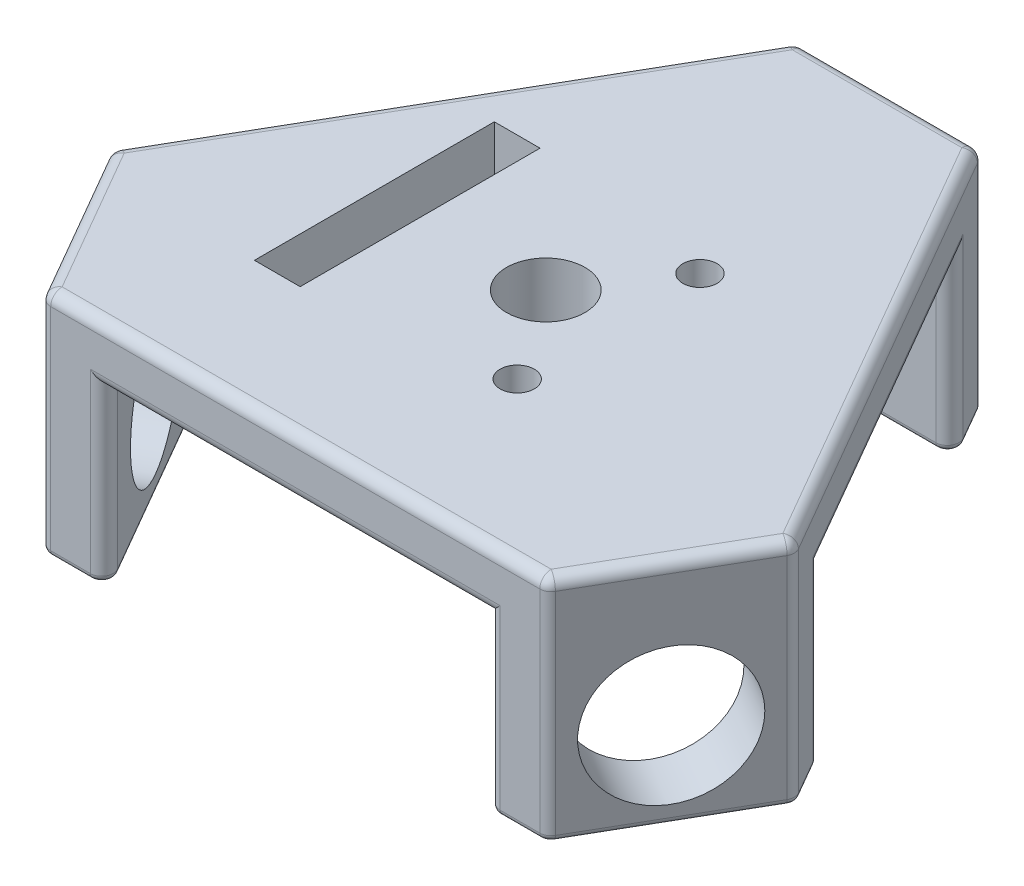
SolidWorks part; units mm, degrees
ref_plane "Front Plane" through (0, 0, 0) normal (0, 0, 1) x (1, 0, 0)
ref_plane "Top Plane" through (0, 0, 0) normal (0, 1, 0) x (1, 0, 0)
ref_plane "Right Plane" through (0, 0, 0) normal (1, 0, 0) x (0, 0, -1)
sketch "Sketch1" plane through (0, 0, 0) normal (0, 1, 0) x (1, 0, 0)
  line L0 (0, 0) -> (0, 30) construction
  line L2 (0, 0) -> (25.9808, -15) construction
  line L4 (0, 0) -> (-25.9808, -15) construction
  line L6 (0, 30) -> (8, 30)
  line L7 (25.9808, -15) -> (29.9808, -8.0718)
  line L8 (25.9808, -15) -> (21.9808, -21.9282)
  line L9 (-29.9808, -8.0718) -> (-25.9808, -15)
  line L10 (-25.9808, -15) -> (-21.9808, -21.9282)
  line L11 (0, 30) -> (-8, 30)
  line L12 (-21.9808, -21.9282) -> (21.9808, -21.9282)
  line L13 (-29.9808, -8.0718) -> (-8, 30)
  line L14 (8, 30) -> (29.9808, -8.0718)
  line L15 (0, 0) -> (-13.825, 7.9819) construction
  line L16 (0, 0) -> (13.825, 7.9819) construction
  line L17 (0, 0) -> (0, -15.9637) construction
  dimension "D2" = 8
  dimension "D3" = 8
  dimension "D4" = 90
  dimension "D5" = 30
  dimension "D6" = 30
  dimension "D7" = 30
  dimension "D1" = 6
extrude "Boss-Extrude1" add sketch "Sketch1" along normal blind 5 contours L13 | L14 L6 L11 L13 L9 L10 L12 L8 L7 | L14 | L12 region at (0, 0, 0)
sketch "Sketch2" plane through (0, 0, 0) normal (0, -1, 0) x (1, 0, 0)
  line L6 (8, -30) -> (29.9808, 8.0718)
  line L7 (29.9808, 8.0718) -> (21.9808, 21.9282)
  line L8 (21.9808, 21.9282) -> (-21.9808, 21.9282)
  line L9 (-21.9808, 21.9282) -> (-29.9808, 8.0718)
  line L10 (-29.9808, 8.0718) -> (-8, -30)
  line L11 (-8, -30) -> (8, -30)
  line L15 (-21.9808, 21.9282) -> (-29.9808, 8.0718)
  line L51 (-17.6506, 19.4282) -> (-25.6506, 5.5718)
  line L52 (-21.9808, 21.9282) -> (21.9808, 21.9282) construction
  line L53 (-29.9808, 8.0718) -> (-8, -30) construction
  line L54 (-21.9808, 21.9282) -> (-16.2073, 21.9282)
  line L55 (-29.9808, 8.0718) -> (-27.094, 3.0718)
  line L56 (-25.6506, 5.5718) -> (-16.2073, 21.9282)
  line L57 (-17.6506, 19.4282) -> (-27.094, 3.0718)
  line L58 (29.9808, 8.0718) -> (21.9808, 21.9282)
  line L59 (21.9808, 21.9282) -> (16.2073, 21.9282)
  line L60 (25.6506, 5.5718) -> (17.6506, 19.4282)
  line L61 (25.6506, 5.5718) -> (16.2073, 21.9282)
  line L62 (17.6506, 19.4282) -> (27.094, 3.0718)
  line L63 (29.9808, 8.0718) -> (27.094, 3.0718)
  line L64 (-8, -30) -> (8, -30)
  line L65 (8, -30) -> (10.8868, -25)
  line L66 (-8, -25) -> (8, -25)
  line L67 (-8, -25) -> (10.8868, -25)
  line L68 (8, -25) -> (-10.8868, -25)
  line L69 (-8, -30) -> (-10.8868, -25)
  line M7 (8, -30) -> (29.9808, 8.0718)
  line M8 (29.9808, 8.0718) -> (21.9808, 21.9282)
  line M9 (21.9808, 21.9282) -> (-21.9808, 21.9282)
  line M10 (-21.9808, 21.9282) -> (-29.9808, 8.0718)
  line M11 (-29.9808, 8.0718) -> (-8, -30)
  line M12 (-8, -30) -> (8, -30)
  dimension "D3" = 3
  dimension "D1" = 0
  dimension "D2" = 5
extrude "Boss-Extrude2" add sketch "Sketch2" along normal blind 15 contours L51 M9 M10 M11 | M7 M8 M9 | M11 M12 M7 region at (0, 0, -27.3726) region at (23.7054, 0, 13.6863) region at (-23.7054, 0, 13.6863)
sketch "Sketch4" plane through (0, 0, -30) normal (0, 0, -1) x (-1, 0, 0)
  line L0 (-10.8868, 0) -> (10.8868, 0) construction
  line L4 (10.8868, -15) -> (-10.8868, -15) construction
  line L6 (-8, 5) -> (-8, -15) construction
  line L7 (-8, -15) -> (8, -15) construction
  line L12 (8, -15) -> (8, 5) construction
  line L14 (-8, 0) -> (8, 0)
  line L21 (8, -15) -> (-8, -15)
  line L23 (-8, 0) -> (-8, -15)
  line L24 (-8, -15) -> (8, -15)
  line L25 (8, -15) -> (8, 0)
  line L31 (-8, -7.5) -> (8, -7.5) construction
  line L32 (0, 0) -> (0, -15) construction
  circle A1 centre (0, -7.5) radius 6
  dimension "D1" = 12
extrude "Cut-Extrude1" cut sketch "Sketch4" against normal up to surface (5 mm away) contours A1 region at (0, -7.5, -30) up to face at (0, -7.5, -25)
pattern_circular "CirPattern1" count 3 over 360 about axis through (0, 5, 0) along (0, 1, 0) of "Cut-Extrude1"
fillet "Fillet1" radius 1 15 edges at (21.9808, -5, 21.9282) (29.9808, -5, 8.0718) (8, -5, -30) (-8, -5, -30) (-29.9808, -5, 8.0718) (-21.9808, -5, 21.9282) (18.9904, 0, -10.9641) (-18.9904, 0, -10.9641) (0, 0, 21.9282) (-16.2073, -7.5, 21.9282) (-27.094, -7.5, 3.0718) (16.2073, -7.5, 21.9282) (27.094, -7.5, 3.0718) (10.8868, -7.5, -25) (-10.8868, -7.5, -25)
fillet "Fillet2" radius 0.5 24 edges at (-19.6714, -15, 21.9282) (19.6714, -15, 21.9282) (-21.6506, -15, 12.5) (-25.9808, -15, 15) (-21.9034, -15, 21.7942) (-29.8261, -15, 8.0718) (-27.094, -15, 4.0718) (-17.0733, -15, 21.4282) (21.6506, -15, 12.5) (25.9808, -15, 15) (29.8261, -15, 8.0718) (21.9034, -15, 21.7942) (27.094, -15, 4.0718) (17.0733, -15, 21.4282) (0, -15, -25) (0, -15, -30) (-7.9226, -15, -29.866) (7.9226, -15, -29.866) (-10.0207, -15, -25.5) (10.0207, -15, -25.5) (9.1547, -15, -28) (28.8261, -15, 6.0718) (-28.8261, -15, 6.0718) (-9.1547, -15, -28)
fillet "Fillet4" radius 1 12 edges at (29.8261, 5, 8.0718) (18.9904, 5, -10.9641) (7.9226, 5, -29.866) (0, 5, -30) (-7.9226, 5, -29.866) (-18.9904, 5, -10.9641) (-29.8261, 5, 8.0718) (-25.9808, 5, 15) (-21.9034, 5, 21.7942) (0, 5, 21.9282) (21.9034, 5, 21.7942) (25.9808, 5, 15)
sketch "Sketch5" plane through (0, 5, 0) normal (0, 1, 0) x (1, 0, 0)
  line L0 (0, 0) -> (0, 10.5) construction
  line L1 (-8, 10.5) -> (8, 10.5)
  line L2 (-8, -10.5) -> (8, -10.5)
  line L3 (-8, 10.5) -> (-8, -10.5)
  line L4 (8, 10.5) -> (8, -10.5)
  line L10 (-11, 10.5) -> (-15, 10.5)
  line L11 (-11, 10.5) -> (-11, -10.5)
  line L12 (-11, -10.5) -> (-15, -10.5)
  line L13 (-15, 10.5) -> (-15, -10.5)
  circle A0 centre (5.5, 8) radius 1.5
  circle A1 centre (5.5, -8) radius 1.5
  point P7 (0, 10.5)
  dimension "D5" = 3
  dimension "D1" = 16
  dimension "D2" = 10.5
  dimension "D6" = 2.5
  dimension "D7" = 2.5
  dimension "D8" = 2.5
  dimension "D9" = 2.5
  dimension "D4" = 4
  dimension "D10" = 21
  dimension "D11" = 3
  dimension "D3" = 21
sketch "Sketch6" plane through (0, 5, 0) normal (0, 1, 0) x (1, 0, 0)
  circle A0 centre (0, 0) radius 3.4311
extrude "Cut-Extrude2" cut sketch "Sketch6" against normal blind 10
extrude "Cut-Extrude3" cut sketch "Sketch5" against normal up to surface (5 mm away) contours A0 | A1 | L11 L10 L13 L12 region at (5.5, 5, -8) region at (5.5, 5, 8) up to face at (0, 0, 3.4311)
